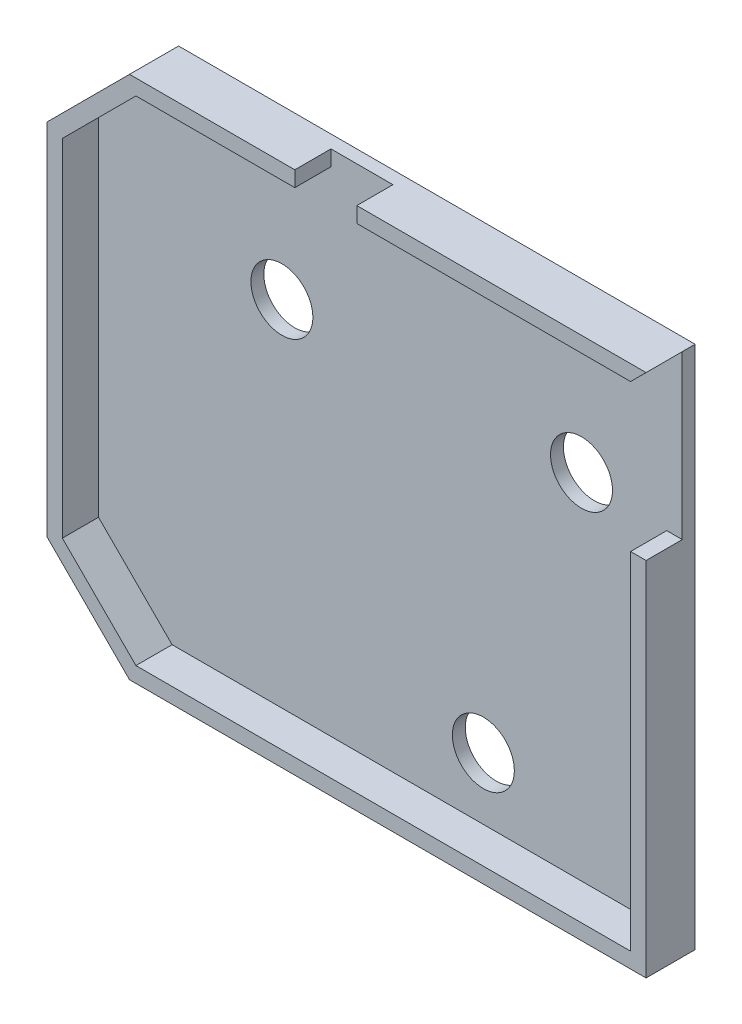
SolidWorks part; units mm, degrees
ref_plane "Plan de face" through (0, 0, 0) normal (0, 0, 1) x (1, 0, 0)
ref_plane "Plan de dessus" through (0, 0, 0) normal (0, 1, 0) x (1, 0, 0)
ref_plane "Plan de droite" through (0, 0, 0) normal (1, 0, 0) x (0, 0, -1)
sketch "Esquisse1" plane through (0, 0, 0) normal (0, 0, 1) x (1, 0, 0)
  line L0 (0, -85) -> (16, -101)
  line L4 (116, 0.5) -> (116, -101)
  line L5 (16, 0.5) -> (0, -15.5)
  line L7 (116, 0.5) -> (16, 0.5)
  line L8 (0, -15.5) -> (0, -85)
  line L9 (16, -101) -> (116, -101)
  dimension "D1" = 101.5
  dimension "D2" = 116
  dimension "D3" = 16
  dimension "D4" = 16
  dimension "D5" = 16
  dimension "D6" = 16
extrude "Boss.-Extru.1" add sketch "Esquisse1" along normal blind 2.5
sketch "Esquisse2" plane through (0, 0, 2.5) normal (0, 0, 1) x (1, 0, 0)
  line L0 (0, -15.5) -> (0, -85) construction
  line L1 (3, -2.5) -> (113, -2.5) construction
  line L2 (3, -2.5) -> (3, -98) construction
  line L3 (3, -98) -> (113, -98) construction
  line L4 (113, -2.5) -> (113, -98) construction
  line L5 (16, -101) -> (116, -101) construction
  line L6 (116, -101) -> (116, 0.5) construction
  line L7 (116, 0.5) -> (16, 0.5) construction
  line L8 (113, -31) -> (116, -31)
  line L9 (3, -83.7574) -> (17.2426, -98)
  line L10 (0, -85) -> (16, -101) construction
  line L11 (3, -16.7426) -> (17.2426, -2.5)
  line L12 (16, 0.5) -> (0, -15.5) construction
  line L14 (3, -16.7426) -> (3, -83.7574)
  line L15 (17.2426, -98) -> (113, -98)
  line L16 (116, 0.5) -> (116, -101) construction
  line L17 (116, -101) -> (16, -101)
  line L18 (16, -101) -> (0, -85)
  line L19 (0, -85) -> (0, -15.5)
  line L20 (0, -15.5) -> (16, 0.5)
  line L22 (113, -2.5) -> (116, 0.5)
  line L23 (113, -98) -> (113, -31)
  line L24 (116, -31) -> (116, -101)
  line L25 (48, -2.5) -> (48, 0.5)
  line L26 (60, -2.5) -> (60, 0.5)
  line L27 (17.2426, -2.5) -> (48, -2.5)
  line L28 (48, 0.5) -> (16, 0.5)
  line L29 (60, 0.5) -> (116, 0.5)
  line L30 (113, -2.5) -> (60, -2.5)
  point P33 (48, -2.5)
  point P34 (60, -2.5)
  dimension "D1" = 3
  dimension "D2" = 3
  dimension "D3" = 3
  dimension "D4" = 3
  dimension "D5" = 3
  dimension "D6" = 3
  dimension "D7" = 70
  dimension "D8" = 45
  dimension "D9" = 12
extrude "Boss.-Extru.2" add sketch "Esquisse2" along normal blind 7
sketch "Esquisse3" plane through (0, 0, 2.5) normal (0, 0, 1) x (1, 0, 0)
  line L0 (113, -31) -> (113, -98) construction
  line L2 (3, -83.7574) -> (3, -16.7426) construction
  line L3 (113, -31) -> (113, -98) construction
  line L4 (113, -98) -> (17.2426, -98) construction
  line L5 (60, 0.5) -> (48, 0.5) construction
  circle A0 centre (96.5, -29.5) radius 6
  circle A1 centre (38.5, -29.5) radius 6
  circle A2 centre (77.5, -86) radius 6
  dimension "D1" = 16.5
  dimension "D2" = 30
  dimension "D3" = 30
  dimension "D4" = 35.5
  dimension "D5" = 35.5
  dimension "D6" = 12
extrude "Enlèv. mat.-Extru.1" cut sketch "Esquisse3" against normal blind 10
